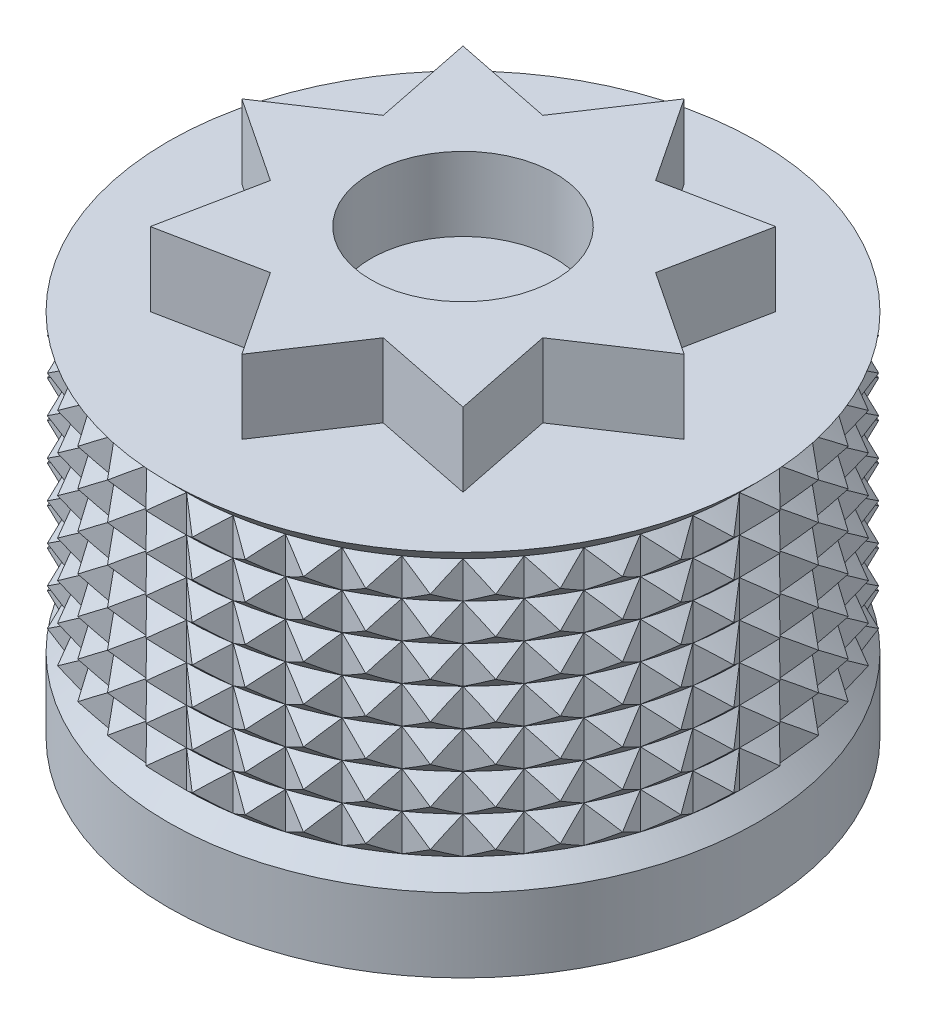
SolidWorks part; units mm, degrees
ref_plane "Front Plane" through (0, 0, 0) normal (0, 0, 1) x (1, 0, 0)
ref_plane "Top Plane" through (0, 0, 0) normal (0, 1, 0) x (1, 0, 0)
ref_plane "Right Plane" through (0, 0, 0) normal (1, 0, 0) x (0, 0, -1)
sketch "Sketch2" plane through (0, 0, 0) normal (0, 0, 1) x (1, 0, 0)
  line L0 (0, 0) -> (0, 12)
  line L1 (0, 0) -> (8, 0)
  line L2 (8, 0) -> (8, 2)
  line L3 (8, 2) -> (7.5, 2.5)
  line L4 (7.5, 2.5) -> (8, 3)
  line L5 (7.5, 3.5) -> (8, 4)
  line L6 (8, 3) -> (7.5, 3.5)
  line L7 (7.5, 4.5) -> (8, 5)
  line L8 (8, 4) -> (7.5, 4.5)
  line L9 (7.5, 5.5) -> (8, 6)
  line L10 (8, 5) -> (7.5, 5.5)
  line L11 (7.5, 6.5) -> (8, 7)
  line L12 (8, 6) -> (7.5, 6.5)
  line L13 (7.5, 7.5) -> (8, 8)
  line L14 (8, 7) -> (7.5, 7.5)
  line L15 (7.5, 8.5) -> (8, 9)
  line L16 (8, 8) -> (7.5, 8.5)
  line L17 (7.5, 9.5) -> (8, 10)
  line L18 (8, 9) -> (7.5, 9.5)
  line L29 (0, 12) -> (7, 12)
  line L30 (8, 11) -> (8, 10)
  arc A0 (7, 12) -> (8, 11) centre (7, 11) cw
  dimension "D7" = 1
  dimension "D1" = 12
  dimension "D2" = 8
  dimension "D3" = 2
  dimension "D4" = 135
  dimension "D5" = 0.5
  dimension "D6" = 8
revolve "Revolve1" add sketch "Sketch2" angle 360 about L0
ref_plane "Plane1" through (0, 9.5, 0) normal (0, 1, 0) x (1, 0, 0)
ref_plane "Plane2" through (0, 2.5, 0) normal (0, 1, 0) x (1, 0, 0)
sketch "Sketch3" plane through (0, 9.5, 0) normal (0, 1, 0) x (1, 0, 0)
  line L0 (0, 0) -> (0, 8.5914) construction
  line L1 (0, 0) -> (0.7361, 9.3536) construction
  line L2 (0, 7.5) -> (0.6277, 7.9753)
  line L3 (0.6277, 7.9753) -> (1.1733, 7.4077)
  line L4 (0, 0) -> (1.5352, 9.6931) construction
  line L5 (1.1733, 7.4077) -> (1.8676, 7.779)
  line L6 (1.8676, 7.779) -> (2.3176, 7.1329)
  line L7 (2.3176, 7.1329) -> (3.0615, 7.391)
  line L8 (3.0615, 7.391) -> (3.4049, 6.6825)
  line L9 (3.4049, 6.6825) -> (4.18, 6.8211)
  line L10 (4.18, 6.8211) -> (4.4084, 6.0676)
  line L11 (4.4084, 6.0676) -> (5.1956, 6.0832)
  line L12 (5.1956, 6.0832) -> (5.3033, 5.3033)
  line L13 (5.3033, 5.3033) -> (6.0832, 5.1956)
  line L14 (6.0832, 5.1956) -> (6.0676, 4.4084)
  line L15 (6.0676, 4.4084) -> (6.8211, 4.18)
  line L16 (6.8211, 4.18) -> (6.6825, 3.4049)
  line L17 (6.6825, 3.4049) -> (7.391, 3.0615)
  line L18 (7.391, 3.0615) -> (7.1329, 2.3176)
  line L19 (7.1329, 2.3176) -> (7.779, 1.8676)
  line L20 (7.779, 1.8676) -> (7.4077, 1.1733)
  line L21 (7.4077, 1.1733) -> (7.9753, 0.6277)
  line L22 (7.9753, 0.6277) -> (7.5, 0)
  line L23 (7.5, 0) -> (7.9753, -0.6277)
  line L24 (7.9753, -0.6277) -> (7.4077, -1.1733)
  line L25 (7.4077, -1.1733) -> (7.779, -1.8676)
  line L26 (7.779, -1.8676) -> (7.1329, -2.3176)
  line L27 (7.1329, -2.3176) -> (7.391, -3.0615)
  line L28 (7.391, -3.0615) -> (6.6825, -3.4049)
  line L29 (6.6825, -3.4049) -> (6.8211, -4.18)
  line L30 (6.8211, -4.18) -> (6.0676, -4.4084)
  line L31 (6.0676, -4.4084) -> (6.0832, -5.1956)
  line L32 (6.0832, -5.1956) -> (5.3033, -5.3033)
  line L33 (5.3033, -5.3033) -> (5.1956, -6.0832)
  line L34 (5.1956, -6.0832) -> (4.4084, -6.0676)
  line L35 (4.4084, -6.0676) -> (4.18, -6.8211)
  line L36 (4.18, -6.8211) -> (3.4049, -6.6825)
  line L37 (3.4049, -6.6825) -> (3.0615, -7.391)
  line L38 (3.0615, -7.391) -> (2.3176, -7.1329)
  line L39 (2.3176, -7.1329) -> (1.8676, -7.779)
  line L40 (1.8676, -7.779) -> (1.1733, -7.4077)
  line L41 (1.1733, -7.4077) -> (0.6277, -7.9753)
  line L42 (0.6277, -7.9753) -> (0, -7.5)
  line L43 (0, -7.5) -> (-0.6277, -7.9753)
  line L44 (-0.6277, -7.9753) -> (-1.1733, -7.4077)
  line L45 (-1.1733, -7.4077) -> (-1.8676, -7.779)
  line L46 (-1.8676, -7.779) -> (-2.3176, -7.1329)
  line L47 (-2.3176, -7.1329) -> (-3.0615, -7.391)
  line L48 (-3.0615, -7.391) -> (-3.4049, -6.6825)
  line L49 (-3.4049, -6.6825) -> (-4.18, -6.8211)
  line L50 (-4.18, -6.8211) -> (-4.4084, -6.0676)
  line L51 (-4.4084, -6.0676) -> (-5.1956, -6.0832)
  line L52 (-5.1956, -6.0832) -> (-5.3033, -5.3033)
  line L53 (-5.3033, -5.3033) -> (-6.0832, -5.1956)
  line L54 (-6.0832, -5.1956) -> (-6.0676, -4.4084)
  line L55 (-6.0676, -4.4084) -> (-6.8211, -4.18)
  line L56 (-6.8211, -4.18) -> (-6.6825, -3.4049)
  line L57 (-6.6825, -3.4049) -> (-7.391, -3.0615)
  line L58 (-7.391, -3.0615) -> (-7.1329, -2.3176)
  line L59 (-7.1329, -2.3176) -> (-7.779, -1.8676)
  line L60 (-7.779, -1.8676) -> (-7.4077, -1.1733)
  line L61 (-7.4077, -1.1733) -> (-7.9753, -0.6277)
  line L62 (-7.9753, -0.6277) -> (-7.5, 0)
  line L63 (-7.5, 0) -> (-7.9753, 0.6277)
  line L64 (-7.9753, 0.6277) -> (-7.4077, 1.1733)
  line L65 (-7.4077, 1.1733) -> (-7.779, 1.8676)
  line L66 (-7.779, 1.8676) -> (-7.1329, 2.3176)
  line L67 (-7.1329, 2.3176) -> (-7.391, 3.0615)
  line L68 (-7.391, 3.0615) -> (-6.6825, 3.4049)
  line L69 (-6.6825, 3.4049) -> (-6.8211, 4.18)
  line L70 (-6.8211, 4.18) -> (-6.0676, 4.4084)
  line L71 (-6.0676, 4.4084) -> (-6.0832, 5.1956)
  line L72 (-6.0832, 5.1956) -> (-5.3033, 5.3033)
  line L73 (-5.3033, 5.3033) -> (-5.1956, 6.0832)
  line L74 (-5.1956, 6.0832) -> (-4.4084, 6.0676)
  line L75 (-4.4084, 6.0676) -> (-4.18, 6.8211)
  line L76 (-4.18, 6.8211) -> (-3.4049, 6.6825)
  line L77 (-3.4049, 6.6825) -> (-3.0615, 7.391)
  line L78 (-3.0615, 7.391) -> (-2.3176, 7.1329)
  line L79 (-2.3176, 7.1329) -> (-1.8676, 7.779)
  line L80 (-1.8676, 7.779) -> (-1.1733, 7.4077)
  line L81 (-1.1733, 7.4077) -> (-0.6277, 7.9753)
  line L82 (-0.6277, 7.9753) -> (0, 7.5)
  circle A0 centre (0, 0) radius 7.5 construction
  circle A1 centre (0, 0) radius 8 construction
  point P130 (0, 0)
  dimension "D2" = 0.5
  dimension "D1" = 4.5
  dimension "D3" = 4.5
  dimension "D4" = 40
extrude "Cut-Extrude2" cut sketch "Sketch3" against normal up to surface (7 mm away) flip side to cut up to plane "Plane2"
sketch "Sketch5" plane through (0, 0, 0) normal (0, -1, 0) x (1, 0, 0)
  circle A0 centre (0, 0) radius 7
  circle A1 centre (0, 0) radius 8 construction
  dimension "D1" = 1
extrude "Cut-Extrude4" cut sketch "Sketch5" against normal blind 1
sketch "Sketch4" plane through (0, 1, 0) normal (0, -1, 0) x (1, 0, 0)
  line L0 (-2.5981, 1.5) -> (2.5981, 1.5) construction
  line L1 (-2.7111, 1.7) -> (2.7111, 1.7)
  arc A0 (2.5981, 1.5) -> (-2.5981, 1.5) centre (0, 0) cw construction
  arc A1 (2.7111, 1.7) -> (-2.7111, 1.7) centre (0, 0) cw
  dimension "D1" = 3
  dimension "D2" = 1.5
  dimension "D3" = 0.2
extrude "Cut-Extrude3" cut sketch "Sketch4" against normal blind 8
sketch "Sketch6" plane through (0, 1, 0) normal (0, -1, 0) x (1, 0, 0)
  line L0 (-2.4, 1.7) -> (-2.2, 1.35)
  line L1 (-2.2, 1.35) -> (-2, 1.7)
  line L2 (-2.4, 1.7) -> (-2, 1.7)
  line L3 (2.7111, 1.7) -> (-2.7111, 1.7) construction
  line L4 (0, 0) -> (0, 3.2663) construction
  line L5 (-3.2, 0.2) -> (-3.2, -0.2)
  line L6 (0, 0) -> (-3.6545, 0) construction
  line L7 (-3.2, 0.2) -> (-2.85, 0)
  line L8 (-2.85, 0) -> (-3.2, -0.2)
  line L9 (-2.9699, -1.2082) -> (-2.7963, -1.5686)
  line L10 (-2.9699, -1.2082) -> (-2.5678, -1.2366)
  line L11 (-2.5678, -1.2366) -> (-2.7963, -1.5686)
  line L12 (-2.1515, -2.3772) -> (-1.8388, -2.6266)
  line L13 (-2.1515, -2.3772) -> (-1.7769, -2.2282)
  line L14 (-1.7769, -2.2282) -> (-1.8388, -2.6266)
  line L15 (-0.9071, -3.0753) -> (-0.5171, -3.1643)
  line L16 (-0.9071, -3.0753) -> (-0.6342, -2.7785)
  line L17 (-0.6342, -2.7785) -> (-0.5171, -3.1643)
  line L18 (0.5171, -3.1643) -> (0.9071, -3.0753)
  line L19 (0.5171, -3.1643) -> (0.6342, -2.7785)
  line L20 (0.6342, -2.7785) -> (0.9071, -3.0753)
  line L21 (1.8388, -2.6266) -> (2.1515, -2.3772)
  line L22 (1.8388, -2.6266) -> (1.7769, -2.2282)
  line L23 (1.7769, -2.2282) -> (2.1515, -2.3772)
  line L24 (2.7963, -1.5686) -> (2.9699, -1.2082)
  line L25 (2.7963, -1.5686) -> (2.5678, -1.2366)
  line L26 (2.5678, -1.2366) -> (2.9699, -1.2082)
  line L27 (3.2, -0.2) -> (3.2, 0.2)
  line L28 (3.2, -0.2) -> (2.85, 0)
  line L29 (2.85, 0) -> (3.2, 0.2)
  line L30 (-1.3, 1.7) -> (-1.1, 1.35)
  line L31 (-1.1, 1.35) -> (-0.9, 1.7)
  line L32 (-1.3, 1.7) -> (-0.9, 1.7)
  line L33 (-0.2, 1.7) -> (0, 1.35)
  line L34 (0, 1.35) -> (0.2, 1.7)
  line L35 (-0.2, 1.7) -> (0.2, 1.7)
  line L36 (0.9, 1.7) -> (1.1, 1.35)
  line L37 (1.1, 1.35) -> (1.3, 1.7)
  line L38 (0.9, 1.7) -> (1.3, 1.7)
  line L39 (2, 1.7) -> (2.2, 1.35)
  line L40 (2.2, 1.35) -> (2.4, 1.7)
  line L41 (2, 1.7) -> (2.4, 1.7)
  arc A0 (-2.7111, 1.7) -> (2.7111, 1.7) centre (0, 0) ccw construction
  arc A1 (-2.7111, 1.7) -> (2.7111, 1.7) centre (0, 0) ccw construction
  point P5 (-2.2, 1.7)
  point P17 (-3.2, 0)
  point P44 (0, 0)
  dimension "D1" = 0.4
  dimension "D2" = 0.35
  dimension "D3" = 2
  dimension "D4" = 90
  dimension "D5" = 0.4
  dimension "D6" = 0.35
  dimension "D8" = 5
  dimension "D7" = 8
extrude "Boss-Extrude2" add sketch "Sketch6" against normal up to surface (8 mm away) from offset 1 up to face at (0, 9, -0.75) offset against normal yes
sketch "Sketch7" plane through (0, 12, 0) normal (0, 1, 0) x (1, 0, 0)
  line L0 (0, 0) -> (0, 8.9713) construction
  line L1 (0, 0) -> (3.4051, 8.2205) construction
  line L2 (0, 0) -> (-3.5263, 8.5132) construction
  line L3 (-1.5307, 3.6955) -> (0, 6)
  line L4 (0, 6) -> (1.5307, 3.6955)
  line L5 (1.5307, 3.6955) -> (4.2426, 4.2426)
  line L6 (4.2426, 4.2426) -> (3.6955, 1.5307)
  line L7 (3.6955, 1.5307) -> (6, 0)
  line L8 (6, 0) -> (3.6955, -1.5307)
  line L9 (3.6955, -1.5307) -> (4.2426, -4.2426)
  line L10 (4.2426, -4.2426) -> (1.5307, -3.6955)
  line L11 (1.5307, -3.6955) -> (0, -6)
  line L12 (0, -6) -> (-1.5307, -3.6955)
  line L13 (-1.5307, -3.6955) -> (-4.2426, -4.2426)
  line L14 (-4.2426, -4.2426) -> (-3.6955, -1.5307)
  line L15 (-3.6955, -1.5307) -> (-6, 0)
  line L16 (-6, 0) -> (-3.6955, 1.5307)
  line L17 (-3.6955, 1.5307) -> (-4.2426, 4.2426)
  line L18 (-4.2426, 4.2426) -> (-1.5307, 3.6955)
  circle A0 centre (0, 0) radius 2.5
  circle A1 centre (0, 0) radius 4 construction
  circle A2 centre (0, 0) radius 6 construction
  point P34 (0, 0)
  dimension "D1" = 5
  dimension "D2" = 8
  dimension "D3" = 12
  dimension "D4" = 22.5
  dimension "D5" = 22.5
  dimension "D6" = 8
extrude "Cut-Extrude5" cut sketch "Sketch7" against normal blind 2 flip side to cut
